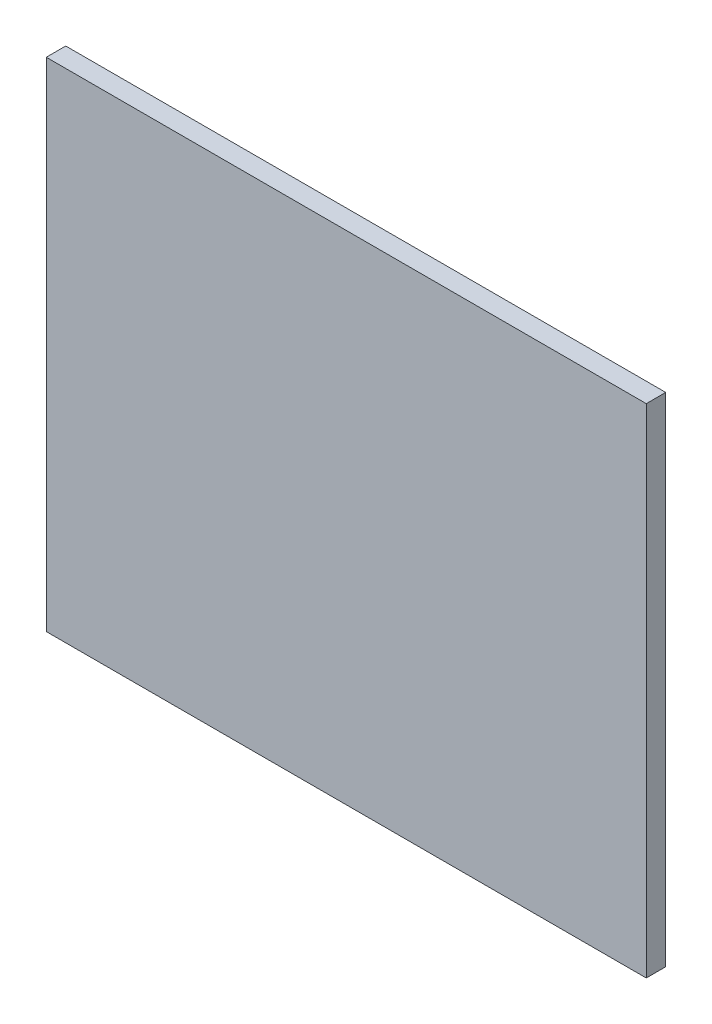
SolidWorks part; units mm, degrees
ref_plane "Front Plane" through (0, 0, 0) normal (0, 0, 1) x (1, 0, 0)
ref_plane "Top Plane" through (0, 0, 0) normal (0, 1, 0) x (1, 0, 0)
ref_plane "Right Plane" through (0, 0, 0) normal (1, 0, 0) x (0, 0, -1)
sketch "Sketch1" plane through (0, 0, 0) normal (0, 0, 1) x (1, 0, 0)
  line L1 (-43.3555, 21.6286) -> (15.1445, 21.6286)
  line L2 (-43.3555, 21.6286) -> (-43.3555, -26.8714)
  line L3 (-43.3555, -26.8714) -> (15.1445, -26.8714)
  line L4 (15.1445, 21.6286) -> (15.1445, -26.8714)
  dimension "D1" = 58.5
  dimension "D2" = 48.5
base flange "Base-Flange1" sketch "Sketch1" thickness 1.8974 reverse thickness direction no parameters "D1"=2.54
sketch "Bend-Lines1" plane through (0, 0, 0) normal (0, 1, 0) x (1, 0, 0)
sketch "Bounding-Box1" plane through (0, 0, 0) normal (0, 1, 0) x (1, 0, 0)
sheet metal parameters "Sheet-Metal1" thickness 1.8974 parameters "D1"=2.54
flat pattern "Flat-Pattern1" [suppressed]
sketch "Bend-Lines2" plane through (0, 0, 0) normal (0, 1, 0) x (1, 0, 0)
sketch "Bounding-Box2" [suppressed] plane through (0, 0, 0) normal (0, 1, 0) x (1, 0, 0)
